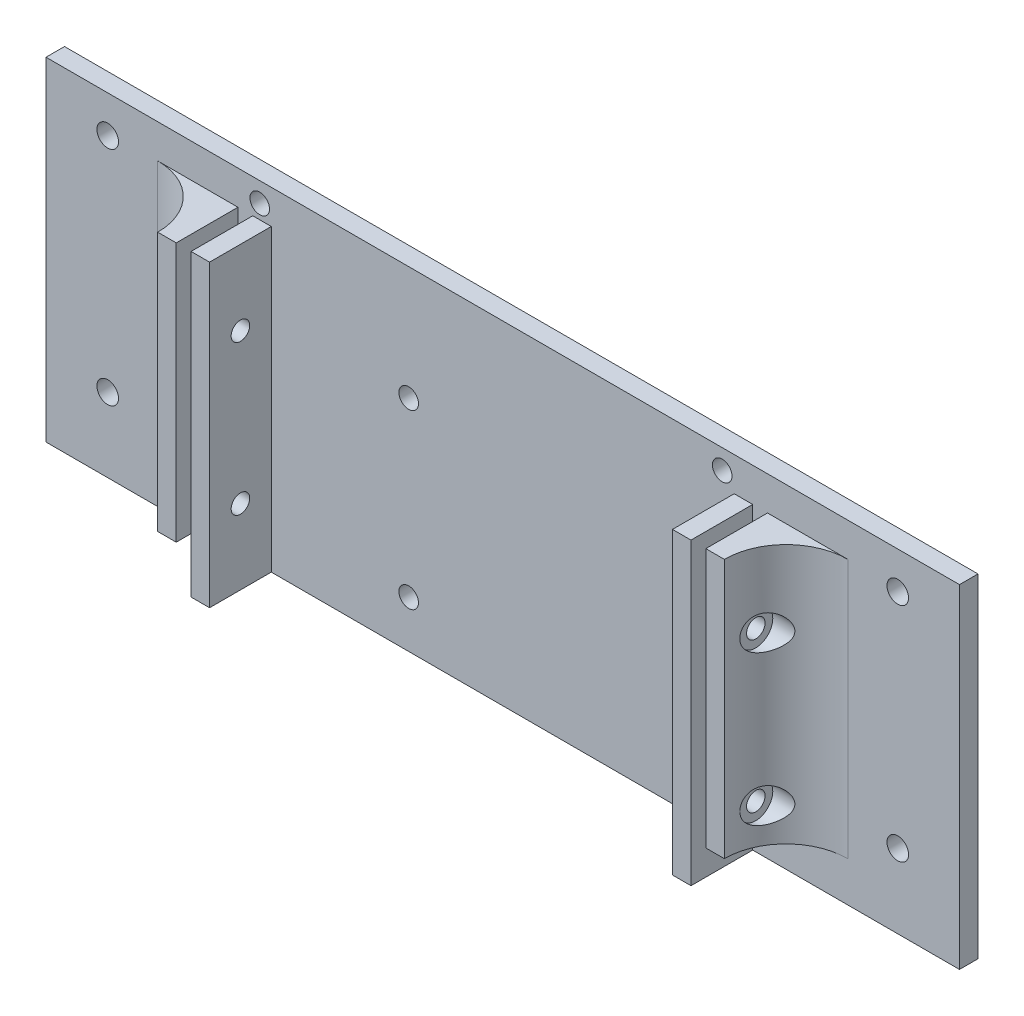
SolidWorks part; units mm, degrees
ref_plane "Front" through (0, 0, 0) normal (0, 0, 1) x (1, 0, 0)
ref_plane "Top" through (0, 0, 0) normal (0, 1, 0) x (1, 0, 0)
ref_plane "Right" through (0, 0, 0) normal (1, 0, 0) x (0, 0, -1)
sketch "Sketch1" plane through (0, 0, 0) normal (0, 1, 0) x (1, 0, 0)
  line L0 (-37.5, -10) -> (-37.5, 0)
  line L1 (-37.5, 0) -> (37.5, 0)
  line L2 (37.5, 0) -> (37.5, -10)
  line L3 (37.5, -10) -> (40.5, -10)
  line L4 (40.5, -10) -> (40.5, 0)
  line L5 (40.5, 0) -> (55.5, 0)
  line L6 (55.5, 0) -> (55.5, 3)
  line L7 (55.5, 3) -> (-55.5, 3)
  line L8 (-55.5, 3) -> (-55.5, 0)
  line L9 (-55.5, 0) -> (-40.5, 0)
  line L10 (-40.5, 0) -> (-40.5, -10)
  line L11 (-40.5, -10) -> (-37.5, -10)
  point P2 (0, 0)
  dimension "D1" = 81
  dimension "D2" = 3
  dimension "D3" = 3
  dimension "D4" = 10
  dimension "D5" = 3
  dimension "D6" = 15
  dimension "D7" = 15
extrude "Boss-Extrude1" add sketch "Sketch1" along normal blind 54
sketch "Sketch2" plane through (-40.5, 0, 0) normal (-1, 0, 0) x (0, 0, 1)
  line L0 (10, 54) -> (10, 48.5)
  line L1 (10, 54) -> (10, 0) construction
  line L2 (10, 48.5) -> (0, 48.5)
  line L3 (0, 54) -> (0, 0) construction
  line L4 (0, 48.5) -> (0, 54)
  line L5 (0, 54) -> (10, 54)
  dimension "D1" = 5.5
extrude "Cut-Extrude1" cut sketch "Sketch2" against normal blind 85
sketch "Sketch3" plane through (0, 0, -3) normal (0, 0, -1) x (-1, 0, 0)
  circle A0 centre (45.72, 2.54) radius 1.5875
  circle A2 centre (-35.56, 50.8) radius 1.5875
  circle A3 centre (39.37, 50.8) radius 1.5875
sketch "Sketch5" plane through (0, 0, -3) normal (0, 0, -1) x (-1, 0, 0)
  circle A1 centre (15.24, 35.56) radius 1.5875
  circle A2 centre (15.24, 7.62) radius 1.5875
extrude "Cut-Extrude4" cut sketch "Sketch5" against normal blind 85
extrude "Cut-Extrude5" cut sketch "Sketch3" against normal blind 10
sketch "Sketch6" plane through (0, 0, -3) normal (0, 0, -1) x (-1, 0, 0)
  line L0 (-55.5, 54) -> (-74, 54)
  line L1 (-74, 54) -> (-74, 0)
  line L2 (-74, 0) -> (-55.5, 0)
  line L3 (-55.5, 0) -> (-55.5, 54)
  line L4 (0, 0) -> (0, 54) construction
  line L5 (-55.5, 54) -> (55.5, 54) construction
  line L6 (55.5, 0) -> (55.5, 54)
  line L7 (74, 0) -> (55.5, 0)
  line L8 (74, 54) -> (74, 0)
  line L9 (55.5, 54) -> (74, 54)
  dimension "D1" = 18.5
extrude "Boss-Extrude2" add sketch "Sketch6" against normal blind 3
sketch "Sketch7" plane through (0, 0, 0) normal (0, 0, 1) x (1, 0, 0)
  line L0 (0, 0) -> (0, 54) construction
  line L1 (-37.5, 0) -> (37.5, 0) construction
  line L2 (-74, 54) -> (74, 54) construction
  line L3 (-42.9, 6.5) -> (-42.9, 48.5)
  line L5 (-42.9, 48.5) -> (-45.9, 48.5)
  line L6 (-45.9, 48.5) -> (-45.9, 6.5)
  line L7 (-45.9, 6.5) -> (-42.9, 6.5)
  line L8 (-40.5, 48.5) -> (-40.5, 0) construction
  line L9 (-37.5, 48.5) -> (-40.5, 48.5) construction
  line L10 (42.9, 48.5) -> (45.9, 48.5)
  line L11 (45.9, 48.5) -> (45.9, 6.5)
  line L12 (42.9, 6.5) -> (42.9, 48.5)
  line L13 (45.9, 6.5) -> (42.9, 6.5)
  dimension "D1" = 3
  dimension "D2" = 42
  dimension "D3" = 2.4
  dimension "D4" = 0
extrude "Boss-Extrude3" add sketch "Sketch7" along normal blind 10
sketch "Sketch4" plane through (-40.5, 0, 0) normal (-1, 0, 0) x (0, 0, 1)
  line L0 (5, 0) -> (5, 48.5) construction
  line L1 (0, 0) -> (10, 0) construction
  line L2 (0, 48.5) -> (10, 48.5) construction
  line L3 (0, 24.25) -> (10, 24.25) construction
  line L4 (0, 48.5) -> (0, 0) construction
  line L5 (10, 48.5) -> (10, 0) construction
  circle A0 centre (5, 12.125) radius 1.5
  circle A1 centre (5, 36.375) radius 1.5
  dimension "D2" = 3
  dimension "D1" = 12.125
extrude "Cut-Extrude3" cut sketch "Sketch4" against normal through all both and the other way through all
fillet "Fillet1" radius 10 2 edges at (45.9, 27.5, 0) (-45.9, 27.5, 0)
sketch "Sketch8" plane through (74, 0, 0) normal (1, 0, 0) x (0, 0, -1)
  circle A0 centre (-5, 36.375) radius 2.75
  circle A1 centre (-5, 12.125) radius 2.75
  dimension "D1" = 5.5
extrude "Cut-Extrude6" cut sketch "Sketch8" against normal blind 28
sketch "Sketch10" plane through (-74, 0, 0) normal (-1, 0, 0) x (0, 0, 1)
  circle A0 centre (5, 12.125) radius 2.75
  circle A1 centre (5, 36.375) radius 2.75
  dimension "D1" = 5.5
extrude "Cut-Extrude7" cut sketch "Sketch10" against normal blind 28
sketch "Sketch11" plane through (0, 0, -3) normal (0, 0, -1) x (-1, 0, 0)
  line L0 (74, 0) -> (74, 54) construction
  line L1 (-74, 0) -> (74, 0) construction
  line L2 (57.171, 6.9849) -> (0, 0) construction
  line L3 (0, 0) -> (0, 54) construction
  line L4 (-74, 54) -> (74, 54) construction
  circle A0 centre (64, 12) radius 1.75
  circle A1 centre (64, 48) radius 1.75
  circle A2 centre (-64, 48) radius 1.75
  circle A3 centre (-64, 12) radius 1.75
  dimension "D1" = 3.5
  dimension "D2" = 3.5
  dimension "D3" = 10
  dimension "D4" = 10
  dimension "D5" = 36
  dimension "D6" = 12
extrude "Cut-Extrude8" cut sketch "Sketch11" against normal blind 4.3
